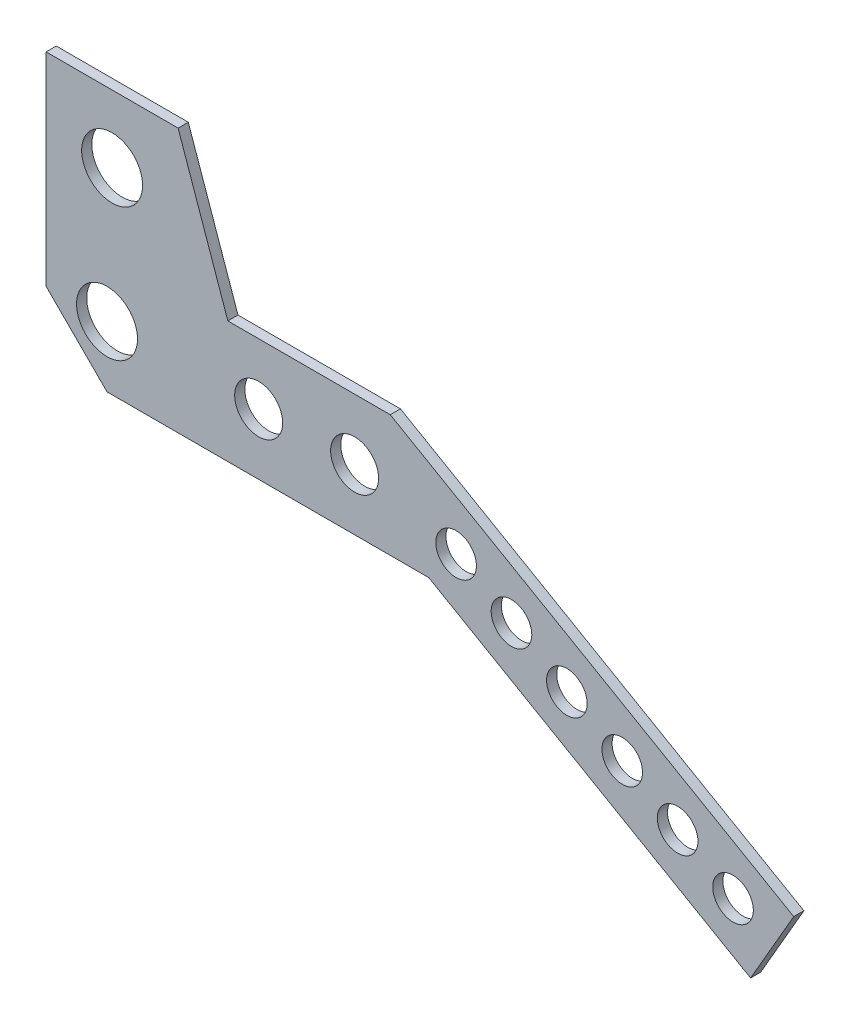
SolidWorks part; units mm, degrees
ref_plane "Front Plane" through (0, 0, 0) normal (0, 0, 1) x (1, 0, 0)
ref_plane "Top Plane" through (0, 0, 0) normal (0, 1, 0) x (1, 0, 0)
ref_plane "Right Plane" through (0, 0, 0) normal (1, 0, 0) x (0, 0, -1)
sketch "Sketch2" plane through (0, 0, 0) normal (0, 0, 1) x (1, 0, 0)
  line L1 (-19.05, 82.55) -> (22.225, 82.55)
  line L2 (22.225, 82.55) -> (37.7757, 38.1)
  line L3 (37.7757, 38.1) -> (88.5757, 38.1)
  line L6 (201.2413, -58.11) -> (100.5918, 0)
  line L7 (100.5918, 0) -> (0, 0)
  line L8 (0, 0) -> (-19.05, 19.05)
  line L9 (-19.05, 19.05) -> (-19.05, 82.55)
  line L10 (88.5757, 38.1) -> (214.7351, -34.7382)
  line L12 (207.9882, -46.4241) -> (109.1511, 10.6395) construction
  line L13 (214.7351, -34.7382) -> (201.2413, -58.11)
  line L16 (115.898, 22.3254) -> (102.4043, -1.0464) construction
  line L17 (47.4154, 38.1) -> (47.4154, 0) construction
  circle A0 centre (109.1511, 10.6395) radius 6.35
  circle A1 centre (126.4716, 0.6395) radius 6.35
  circle A2 centre (143.7921, -9.3605) radius 6.35
  circle A3 centre (161.1127, -19.3605) radius 6.35
  circle A4 centre (178.4332, -29.3605) radius 6.35
  circle A5 centre (195.7537, -39.3605) radius 6.35
  circle A6 centre (47.4154, 19.05) radius 7.5
  circle A7 centre (77.4154, 19.05) radius 7.5
  circle A8 centre (0, 19.05) radius 9.525
  circle A9 centre (1.5875, 61.4462) radius 9.525
  point P35 (0, 0)
  point P36 (1.5875, 82.55)
  dimension "D7" = 12.7
  dimension "D15" = 15
  dimension "D16" = 15
  dimension "D18" = 19.05
  dimension "D1" = 41.275
  dimension "D2" = 50.8
  dimension "D3" = 63.5
  dimension "D4" = 19.05
  dimension "D5" = 135
  dimension "D6" = 38.1
  dimension "D8" = 20
  dimension "D9" = 20
  dimension "D10" = 20
  dimension "D11" = 20
  dimension "D12" = 20
  dimension "D13" = 150
  dimension "D14" = 26.9875
  dimension "D17" = 30
  dimension "D19" = 19.05
  dimension "D20" = 19.05
extrude "Boss-Extrude1" add sketch "Sketch2" along normal blind 3.175
